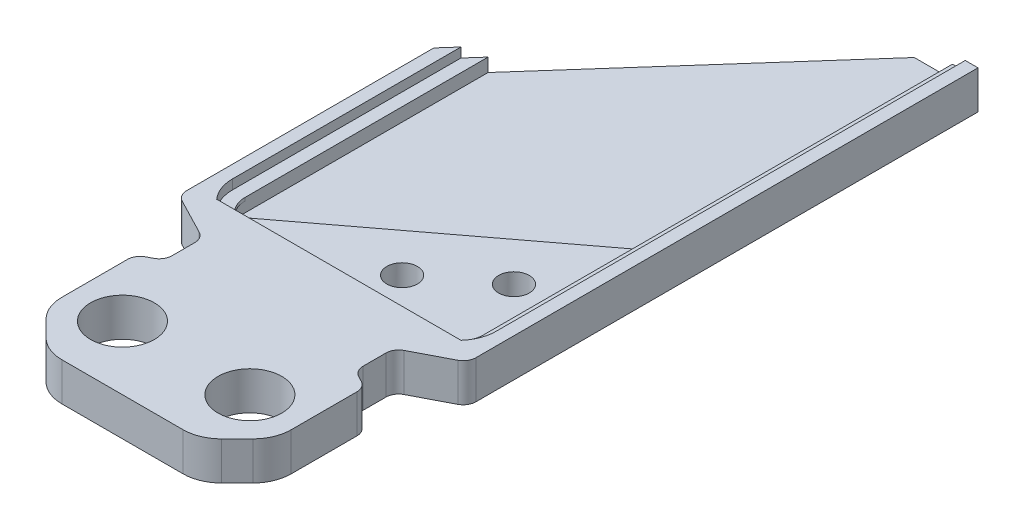
SolidWorks part; units mm, degrees
ref_plane "Front Plane" through (0, 0, 0) normal (0, 0, 1) x (1, 0, 0)
ref_plane "Top Plane" through (0, 0, 0) normal (0, 1, 0) x (1, 0, 0)
ref_plane "Right Plane" through (0, 0, 0) normal (1, 0, 0) x (0, 0, -1)
sketch "Sketch1" plane through (0, 0, 0) normal (0, 1, 0) x (1, 0, 0)
  line L0 (-9, 0) -> (-9, 10)
  line L30 (-9, 10) -> (-7.5, 10.7792)
  line L31 (-7.5, 10.7792) -> (-7.5, 13.7792)
  line L32 (-7.5, 13.7792) -> (-11.35, 15.7792)
  line L33 (-11.35, 15.7792) -> (-11.35, 35.7792)
  line L34 (-11.35, 35.7792) -> (6.35, 55.7792)
  line L35 (6.35, 55.7792) -> (11.35, 55.7792)
  line L36 (11.35, 55.7792) -> (11.35, 15.7792)
  line L37 (11.35, 15.7792) -> (7.5, 13.7792)
  line L38 (7.5, 13.7792) -> (7.5, 10.7792)
  line L39 (7.5, 10.7792) -> (9, 10)
  line L40 (9, 10) -> (9, 0)
  line L41 (9, 0) -> (-9, 0)
  line L42 (0, -223.5579) -> (0, 227.3148) construction
  line L43 (-9.35, 35.7792) -> (9.35, 35.7792) construction
  line L44 (-9.35, 35.7792) -> (-11.35, 35.7792) construction
  line L45 (9.35, 35.7792) -> (11.35, 35.7792) construction
  point P19 (0, 35.7792)
  point P20 (0, 0)
  dimension "D1" = 3
  dimension "D2" = 18
  dimension "D3" = 18.7
  dimension "D4" = 5
  dimension "D5" = 40
  dimension "D6" = 20
  dimension "D8" = 2
  dimension "D9" = 15
  dimension "D10" = 2
  dimension "D7" = 10
extrude "Boss-Extrude1" add sketch "Sketch1" along normal mid plane 3
sketch "Sketch2" plane through (0, 0, 0) normal (0, 1, 0) x (1, 0, 0)
  line L0 (-5, 5) -> (5, 5) construction
  line L1 (-9, 0) -> (-9, 10) construction
  line L2 (9, 0) -> (-9, 0) construction
  circle A0 centre (-5, 5) radius 2.5
  circle A1 centre (5, 5) radius 2.5
  point P4 (0, 5)
  dimension "D2" = 5
  dimension "D1" = 4
  dimension "D3" = 5
extrude "Cut-Extrude1" cut sketch "Sketch2" against normal through all both and the other way through all
sketch "Sketch3" plane through (0, 0, 0) normal (0, 1, 0) x (1, 0, 0)
  line L0 (-11.35, 35.7792) -> (6.35, 55.7792) construction
  line L1 (6.35, 55.7792) -> (11.35, 55.7792) construction
  line L3 (6.35, 55.7792) -> (9.35, 55.7792)
  line L4 (-9.35, 38.0391) -> (6.35, 55.7792)
  line L6 (-7.35, 18.4899) -> (-9.35, 16.9792) construction
  line L7 (-7.35, 18.4899) -> (9.35, 31.1042) construction
  line L8 (-7.35, 18.4899) -> (-9.35, 16.9792)
  line L9 (-7.35, 18.4899) -> (9.35, 31.1042)
  line L63 (9.35, 31.1042) -> (9.35, 55.7792)
  line L70 (-9.35, 38.0391) -> (-9.35, 16.9792)
  dimension "D1" = 18.7
sketch "Sketch4" plane through (0, 0, 0) normal (0, 1, 0) x (1, 0, 0)
  line L0 (-9.35, 16.9792) -> (9.35, 16.9792)
  line L6 (9.35, 16.9792) -> (9.35, 55.7792)
  line L7 (-9.35, 55.7792) -> (-9.35, 16.9792)
  line L8 (-9.35, 55.7792) -> (9.35, 55.7792)
  line L10 (11.35, 55.7792) -> (6.35, 55.7792) construction
  point P10 (0, 16.9792)
  dimension "D1" = 18.7
  dimension "D2" = 1.2
extrude "Cut-Extrude4" cut sketch "Sketch4" along normal through all from surface starting at plane "Top Plane"
extrude "Cut-Extrude5" cut sketch "Sketch4<2>" against normal mid plane 0.6
sketch "Sketch4<2>" plane through (0, 0, 0) normal (0, 1, 0) x (1, 0, 0) same geometry as "Sketch4"
fillet "Fillet6" radius 2 1 edges at (-9.35, 0.6, -16.9792)
sketch "Sketch5" plane through (0, 0, -16.9792) normal (0, 0, -1) x (-1, 0, 0)
  line L1 (7.35, -0.3) -> (7.35, 1.5) construction
  point P1 (7.35, 0.5)
  dimension "D1" = 0.8
extrude "Cut-Extrude6" cut sketch "Sketch4<4>" along normal up to vertex (0.5 mm away) and the other way up to surface (0.3 mm away) up to point (-7.35, 0.5, -16.9792) other way up to face at (-0.2357, -0.3, -33.6868)
sketch "Sketch4<4>" plane through (0, 0, 0) normal (0, 1, 0) x (1, 0, 0) same geometry as "Sketch4"
sketch "Sketch9" plane through (0, -0.3, 0) normal (0, 1, 0) x (1, 0, 0)
  line L0 (9.35, 16.9792) -> (9.35, 55.7792) construction
  line L1 (-9.35, 16.9792) -> (9.35, 16.9792) construction
  line L2 (9.35, 16.9792) -> (9.35, 31.1042)
  line L3 (-9.35, 16.9792) -> (9.35, 16.9792)
  line L5 (-9.35, 16.9792) -> (-7.35, 18.4899)
  line L6 (-7.35, 18.4899) -> (9.35, 31.1042)
extrude "Boss-Extrude2" add sketch "Sketch9" along normal up to vertex (0.8 mm away) up to point (-7.35, 0.5, -16.9792)
fillet "Fillet7" radius 2 1 edges at (9.35, 1, -16.9792)
chamfer "Chamfer1" distance 3 angle 45 2 edges at (9, 0, 0) (-9, 0, 0)
fillet "Fillet2" radius 1 8 edges at (11.35, 0, -15.7792) (9, 0, -10) (7.5, 0, -10.7792) (7.5, 0, -13.7792) (-9, 0, -10) (-7.5, 0, -10.7792) (-7.5, 0, -13.7792) (-11.35, 0, -15.7792)
fillet "Fillet3" radius 3 4 edges at (9, 0, -3) (6, 0, 0) (-6, 0, 0) (-9, 0, -3)
sketch "Sketch10" plane through (0, 1.5, 0) normal (0, 1, 0) x (1, 0, 0)
  line L5 (-10.35, 36.9092) -> (-10.35, 18.9792)
  line L6 (-9.5861, 16.9792) -> (9.5861, 16.9792)
  line L7 (10.35, 18.9792) -> (10.35, 55.7792)
  line L8 (10.35, 55.7792) -> (6.35, 55.7792)
  line L9 (6.35, 55.7792) -> (-10.35, 36.9092)
  line L10 (-10.35, 36.9092) -> (-10.35, 18.9792)
  line L11 (-9.5861, 16.9792) -> (9.5861, 16.9792)
  line L12 (10.35, 18.9792) -> (10.35, 55.7792)
  line L13 (10.35, 55.7792) -> (6.35, 55.7792)
  line L14 (6.35, 55.7792) -> (-10.35, 36.9092)
  arc A2 (-10.35, 18.9792) -> (-9.5861, 16.9792) centre (-7.35, 18.9792) ccw
  arc A3 (9.5861, 16.9792) -> (10.35, 18.9792) centre (7.35, 18.9792) ccw
  arc A4 (-10.35, 18.9792) -> (-9.5861, 16.9792) centre (-7.35, 18.9792) ccw
  arc A5 (9.5861, 16.9792) -> (10.35, 18.9792) centre (7.35, 18.9792) ccw
  dimension "D1" = 0
extrude "Cut-Extrude7" cut sketch "Sketch10" against normal blind 0.75
hole_wizard "CSK for M2 Flat Head Machine Screw1" positions "Sketch11" profile "Sketch12" countersink size "M2" standard "ANSI Metric"
sketch "Sketch11" plane through (-5, 1.5, 32.5) normal (0, 1, 0) x (1, 0, 0)
  line L0 (11.85, 56.3676) -> (6.85, 52.5909) construction
  point P0 (11.85, 56.3676)
  point P2 (6.85, 52.5909)
sketch "Sketch12" plane through (6.85, 1.5, -23.8676) normal (1, 0, 0) x (0, 0, 1)
  line L0 (0, 0) -> (0, 4.721)
  line L1 (0, 4.721) -> (1.2, 4)
  line L2 (1.2, 4) -> (1.2, 1)
  line L3 (1.2, 1) -> (2.2, 0)
  line L4 (2.2, 0) -> (0, 0)
  line L5 (-1.2, 1) -> (-2.2, 0) construction
  line L6 (0, 4.721) -> (-1.2, 4) construction
  line L7 (0, -6.35) -> (0, 107.95) construction
  dimension "Hole Dia." = 2.4
  dimension "Hole Depth" = 4
  dimension "Near C'Sink Dia." = 4.4
  dimension "Near C'Sink Angle" = 90
  dimension "Drill Angle" = 118
